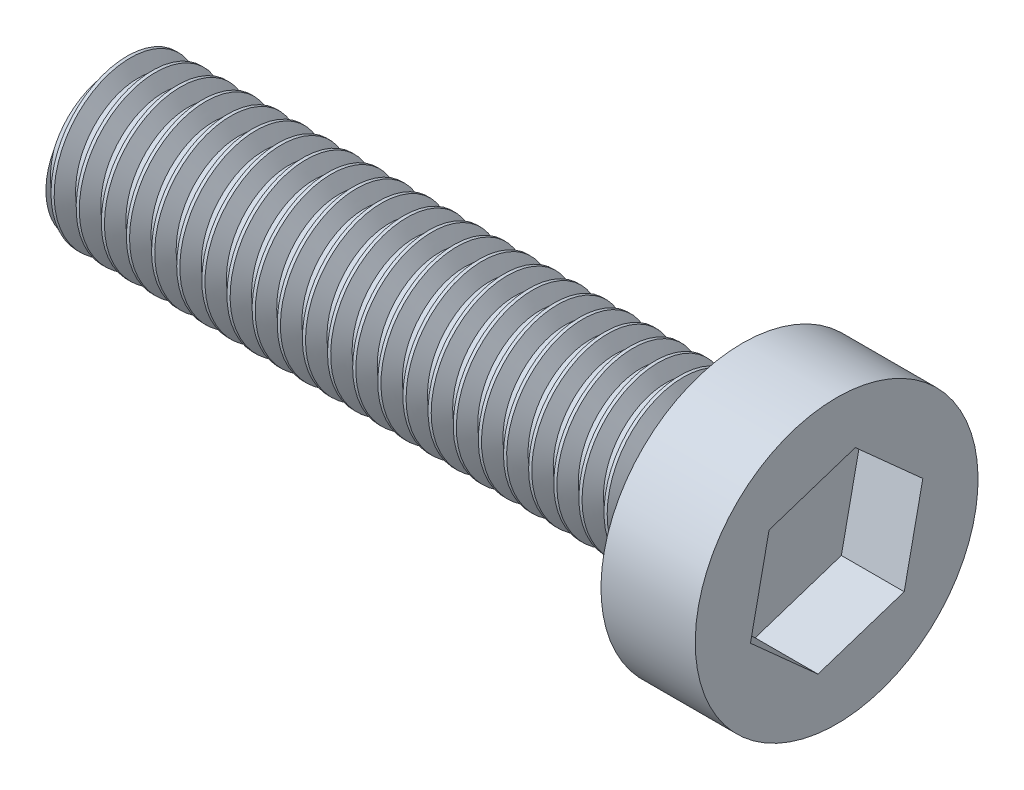
SolidWorks part; units mm, degrees
ref_plane "Front Plane" through (0, 0, 0) normal (0, 0, 1) x (1, 0, 0)
ref_plane "Top Plane" through (0, 0, 0) normal (0, 1, 0) x (1, 0, 0)
ref_plane "Right Plane" through (0, 0, 0) normal (1, 0, 0) x (0, 0, -1)
sketch "Sketch1" plane through (0, 0, 0) normal (0, 0, 1) x (1, 0, 0)
  line L0 (-1.3904, 2.5) -> (18.6096, 2.5)
  line L1 (18.6096, 2.5) -> (18.6096, 4.5)
  line L2 (18.6096, 4.5) -> (21.6096, 4.5)
  line L3 (21.6096, 4.5) -> (21.6096, 0)
  line L4 (21.6096, 0) -> (-1.3904, 0)
  line L5 (-1.3904, 0) -> (-1.3904, 2.5)
  dimension "D1" = 2.5
  dimension "D2" = 20
  dimension "D3" = 3
  dimension "D4" = 2
revolve "Revolve1" add sketch "Sketch1" angle 360 about L4
thread "Thread1" pitch 0.8 method cut trim with start face yes trim with end face yes profile "Thread Profile1" start angle 0, offset 3, length 0, pitch 0.8, diameter 5
ref_plane "Plane1" through (-4.3904, 0, -2.5) normal (0, -1, 0) x (0, 0, -1)
sketch "Thread Profile1" plane through (-4.3904, 0, -2.5) normal (0, -1, 0) x (0, 0, -1)
  line L0 (0, 0) -> (0, 0.8) construction
  line L11 (0, 0) -> (0, 0.7)
  line L12 (0, 0.7) -> (-0.433, 0.45)
  line L13 (-0.433, 0.45) -> (-0.433, 0.25)
  line L15 (-0.433, 0.25) -> (0, 0)
  line L17 (-0.433, 0.35) -> (0, 0.35) construction
  point P2 (0, 0)
  dimension "Pitch" = 0.8
  dimension "Profile_Angle" = 60
  dimension "Profile_Land" = 0.2
  dimension "Profile_Height" = 0.433
sketch "Sketch5" plane through (21.6096, 0, 0) normal (1, 0, 0) x (0, 0, -1)
sketch "Sketch6" plane through (21.6096, 0, 0) normal (1, 0, 0) x (0, 0, -1)
  line L1 (2.15, -1.9263) -> (2.7433, 0.8988)
  line L2 (2.7433, 0.8988) -> (0.5933, 2.8251)
  line L3 (0.5933, 2.8251) -> (-2.15, 1.9263)
  line L4 (-2.15, 1.9263) -> (-2.7433, -0.8988)
  line L5 (-2.7433, -0.8988) -> (-0.5933, -2.8251)
  line L6 (-0.5933, -2.8251) -> (2.15, -1.9263)
  circle A0 centre (0, 0) radius 2.5 construction
  dimension "D1" = 5
extrude "Cut-Extrude1" cut sketch "Sketch6" against normal blind 2
